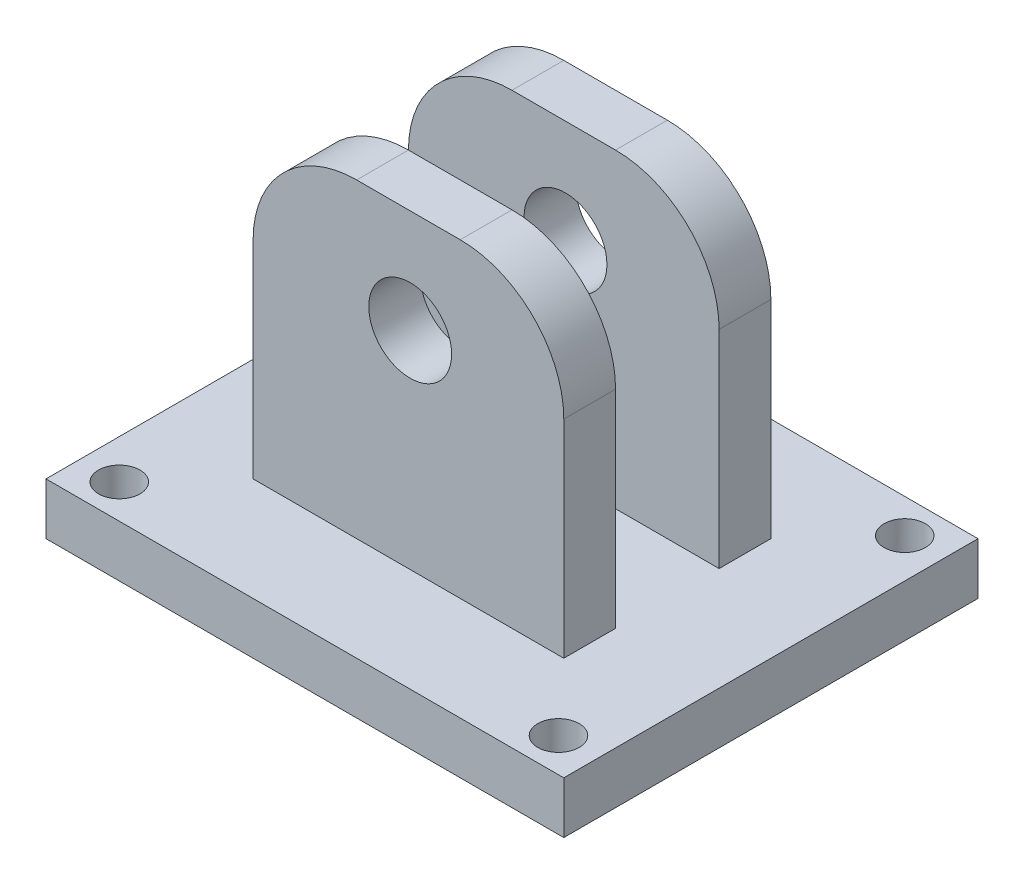
SolidWorks part; units mm, degrees
note: The reader was unsure of these and kept them because the rebuilt part matched: shared geometry of "Sketch5<4>".
material "Stal nierdzewna (ferrytyczna)"
ref_plane "Front Plane" through (0, 0, 0) normal (0, 0, 1) x (1, 0, 0)
ref_plane "Top Plane" through (0, 0, 0) normal (0, 1, 0) x (1, 0, 0)
ref_plane "Right Plane" through (0, 0, 0) normal (1, 0, 0) x (0, 0, -1)
sketch "Sketch1" plane through (0, 0, 0) normal (0, 1, 0) x (1, 0, 0)
  line L1 (-22.332, 12.1542) -> (27.668, 12.1542)
  line L2 (-22.332, 12.1542) -> (-22.332, -27.8458)
  line L3 (-22.332, -27.8458) -> (27.668, -27.8458)
  line L4 (27.668, 12.1542) -> (27.668, -27.8458)
  dimension "D1" = 50
  dimension "D2" = 40
extrude "Boss-Extrude1" add sketch "Sketch1" along normal blind 5 contours L3 L4 L1 L2
sketch "Sketch2" plane through (0, 0, 0) normal (0, 1, 0) x (1, 0, 0)
  line L0 (27.668, 12.1542) -> (27.668, -27.8458) construction
  line L1 (-12.332, -12.8458) -> (17.668, -12.8458)
  line L2 (-12.332, -12.8458) -> (-12.332, -17.8458)
  line L3 (-12.332, -17.8458) -> (17.668, -17.8458)
  line L4 (17.668, -12.8458) -> (17.668, -17.8458)
  line L6 (-22.332, -27.8458) -> (27.668, -27.8458) construction
  line L7 (-22.332, 12.1542) -> (27.668, 12.1542) construction
  line L8 (-12.332, 2.1542) -> (17.668, 2.1542)
  line L9 (-12.332, 2.1542) -> (-12.332, -2.8458)
  line L10 (-12.332, -2.8458) -> (17.668, -2.8458)
  line L11 (17.668, 2.1542) -> (17.668, -2.8458)
  line L12 (27.668, 12.1542) -> (27.668, -27.8458) construction
  dimension "D1" = 5
  dimension "D2" = 30
  dimension "D3" = 10
  dimension "D4" = 10
  dimension "D5" = 10
  dimension "D6" = 10
  dimension "D7" = 10
  dimension "D8" = 30
extrude "Boss-Extrude2" add sketch "Sketch2" along normal blind 35
fillet "Fillet1" radius 10 1 edges at (17.668, 35, 15.3458)
fillet "Fillet2" radius 10 1 edges at (-12.332, 35, 15.3458)
fillet "Fillet3" radius 10 1 edges at (-12.332, 35, 0.3458)
fillet "Fillet4" radius 10 1 edges at (17.668, 35, 0.3458)
sketch "Sketch3" plane through (0, 0, 17.8458) normal (0, 0, 1) x (1, 0, 0)
  line L0 (2.668, 35) -> (3.1666, 5) construction
  line L1 (-2.332, 35) -> (7.668, 35) construction
  line L2 (17.668, 5) -> (-12.332, 5) construction
  line L3 (17.668, 25) -> (-12.332, 25) construction
  circle A0 centre (2.8342, 25) radius 4
  dimension "D1" = 8
extrude "Cut-Extrude1" cut sketch "Sketch3" against normal blind 35 contours A0
sketch "Sketch5" plane through (0, 5, 0) normal (0, 1, 0) x (1, 0, 0)
  line L0 (2.668, -27.8458) -> (2.668, 12.1542) construction
  line L1 (-22.332, -27.8458) -> (27.668, -27.8458) construction
  line L2 (-22.332, 12.1542) -> (27.668, 12.1542) construction
  line L3 (27.668, -7.8458) -> (-22.332, -7.8458) construction
  line L4 (27.668, 12.1542) -> (27.668, -27.8458) construction
  line L5 (-22.332, 12.1542) -> (-22.332, -27.8458) construction
  circle A0 centre (23.874, -24.5645) radius 2
  circle A1 centre (-18.538, -24.5645) radius 2
  circle A2 centre (23.874, 8.8728) radius 2
  circle A3 centre (-18.538, 8.8728) radius 2
  dimension "D1" = 4
extrude "Cut-Extrude3" cut sketch "Sketch5" against normal blind 35 contours A3
extrude "Cut-Extrude4" cut sketch "Sketch5<4>" against normal blind 35
sketch "Sketch5<4>" plane through (0, 5, 0) normal (0, 1, 0) x (1, 0, 0) same geometry as "Sketch5"
sketch "Szkic2" plane through (0, 0, 17.8458) normal (0, 0, 1) x (1, 0, 0)
sketch "Szkic4" plane through (0, 0, 0) normal (0, -1, 0) x (1, 0, 0)
  line L0 (27.668, -12.1542) -> (27.668, -7.4756) construction
  line L1 (27.668, -7.4756) -> (27.668, -12.1542) construction
  line L2 (27.668, -12.1542) -> (21.7195, -12.1542) construction
